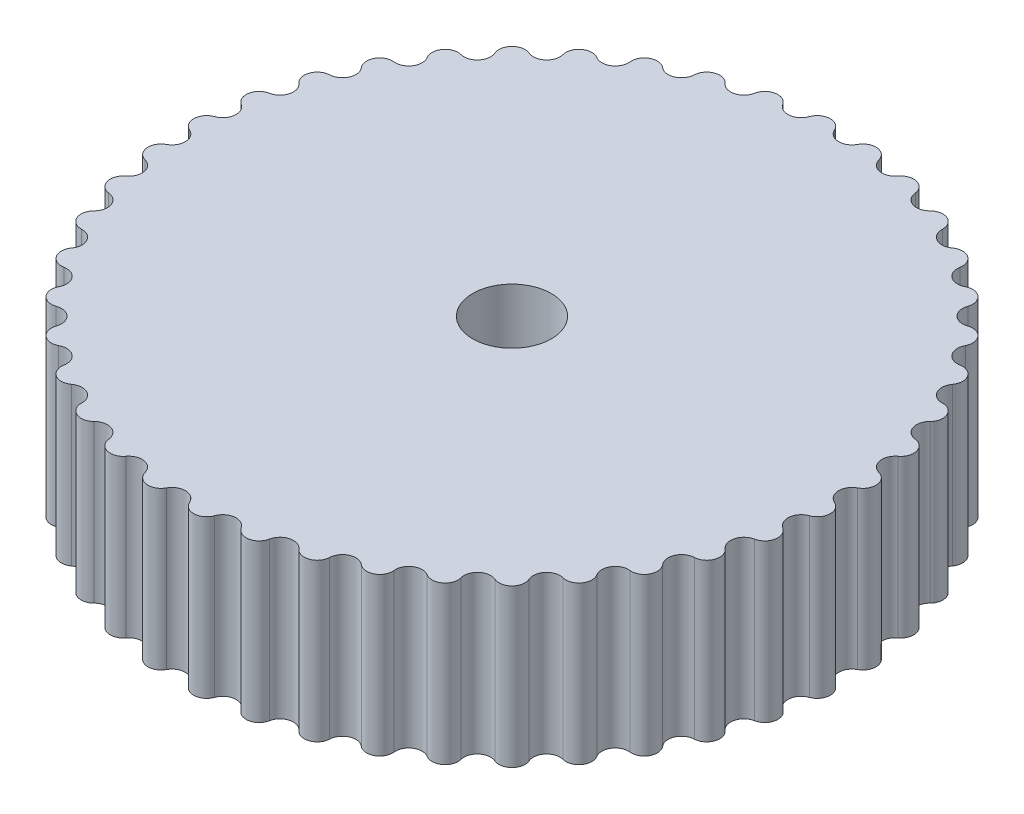
SolidWorks part; units mm, degrees
ref_plane "Front Plane" through (0, 0, 0) normal (0, 0, 1) x (1, 0, 0)
ref_plane "Top Plane" through (0, 0, 0) normal (0, 1, 0) x (1, 0, 0)
ref_plane "Right Plane" through (0, 0, 0) normal (1, 0, 0) x (0, 0, -1)
sketch "Sketch1" plane through (0, 0, 0) normal (0, 1, 0) x (1, 0, 0)
  line L0 (0, 10) -> (0, 10.5) construction
  line L1 (0.7473, 9.972) -> (0.7847, 10.4706) construction
  line L2 (1.4904, 9.8883) -> (1.5649, 10.3827) construction
  line L3 (0, 10.25) -> (0, 1.25)
  line L4 (0.1863, 1.236) -> (1.5277, 10.1355)
  circle A0 centre (0, 0) radius 10 construction
  arc A1 (0, 10.25) -> (0.766, 10.2213) centre (0.3898, 10.4166) ccw
  arc A2 (1.5649, 10.3827) -> (0, 10.5) centre (0, 0) ccw construction
  arc A3 (0.766, 10.2213) -> (1.5277, 10.1355) centre (1.1293, 10.0224) cw
  arc A4 (0.1863, 1.236) -> (0, 1.25) centre (0, 0) ccw
  point P6 (0, 10.25)
  point P9 (0.766, 10.2213)
  dimension "D1" = 20
  dimension "D2" = 0.5
  dimension "D3" = 2.5
extrude "Boss-Extrude1" add sketch "Sketch1" along normal blind 5
pattern_circular "CirPattern1" count 42 over 360 of "Boss-Extrude1" reverse direction yes
ref_axis "Axis1" through (0, 0, 0) along (0, 1, 0)
sketch "Sketch2" plane through (0, 5, 0) normal (0, 1, 0) x (1, 0, 0)
  line L0 (0, 74.1691) -> (0, -78.0459) construction
  line L1 (4.7625, 3.175) -> (6.6675, 3.175)
  line L2 (4.7625, 3.175) -> (4.7625, -3.175)
  line L3 (4.7625, -3.175) -> (6.6675, -3.175)
  line L4 (6.6675, 3.175) -> (6.6675, -3.175)
  line L5 (-6.6675, 3.175) -> (-6.6675, -3.175)
  line L6 (-4.7625, -3.175) -> (-6.6675, -3.175)
  line L7 (-4.7625, 3.175) -> (-4.7625, -3.175)
  line L8 (-4.7625, 3.175) -> (-6.6675, 3.175)
  point P6 (4.7625, 0)
  point P12 (-4.7625, 0)
  dimension "D1" = 1.905
  dimension "D2" = 6.35
  dimension "D3" = 4.7625
